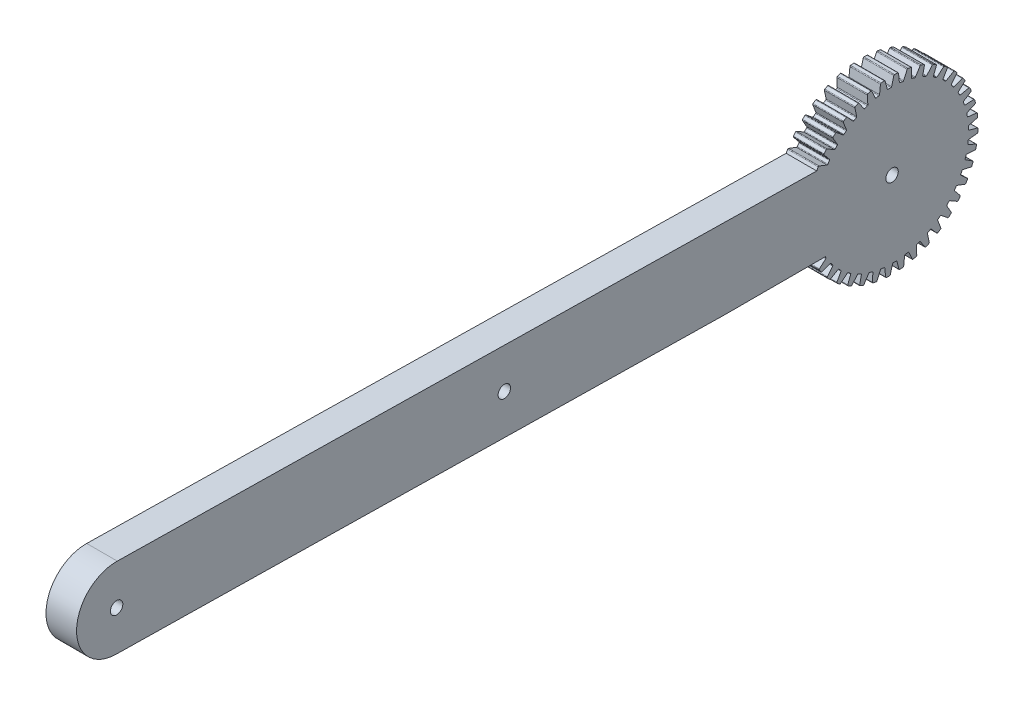
SolidWorks part; units mm, degrees
ref_plane "Front Plane" through (0, 0, 0) normal (0, 0, 1) x (1, 0, 0)
ref_plane "Top Plane" through (0, 0, 0) normal (0, 1, 0) x (1, 0, 0)
ref_plane "Right Plane" through (0, 0, 0) normal (1, 0, 0) x (0, 0, -1)
sketch "Sketch2" plane through (0, 0, 0) normal (1, 0, 0) x (0, 0, -1)
  line L0 (0, 0) -> (-202.971, 3.4315) construction
  line L1 (-0.1772, -10.4815) -> (-203.1482, -7.0501)
  line L2 (0.1772, 10.4815) -> (-202.7938, 13.913)
  arc A0 (-0.1772, -10.4815) -> (0.1772, 10.4815) centre (0, 0) ccw
  arc A1 (-202.7938, 13.913) -> (-203.1482, -7.0501) centre (-202.971, 3.4315) ccw
  circle A2 centre (-202.971, 3.4315) radius 1.625
  circle A3 centre (-101.4855, 1.7157) radius 1.625
  circle A4 centre (0, 0) radius 1.625
  circle A5 centre (0, 0) radius 44.6702
  point P3 (-101.4855, 1.7157)
  point P15 (0, 0)
  dimension "D1" = 3.25
  dimension "D2" = 3.25
  dimension "D3" = 3.25
extrude "Boss-Extrude1" add sketch "Sketch2" along normal blind 8 contours L1 A5 L2 A0 | A4 A5 L1 A0 L2 | A5 L2 A1 L1 A3 A2 region at (0, -0.1984, -11.7372) region at (0, 0.3059, 18.0947) region at (0, 2.1577, 127.6262)
extrude "Cut-Extrude1" cut sketch "Sketch3" against normal through all contours S319 A159 S318 L477 E317 L476 E316 L475 S317 A158 S316 L474 E315 L473 E314 L472 S315 A157 S314 L471 E313 L470 E312 L469 S313 A156 S312 L468 E311 L467 E310 L466 S311 A155 S310 L465 E309 L464 E308 L463 S309 A154 S308 L462 E307 L461 E306 L460 S307 A153 S306 region at (42.0599, 13.0326, 41.9132)
sketch "Sketch3" plane through (42.0599, -65.896, -38.7893) normal (1, 0, 0) x (0, 0, -1)
  line L6 (-58.518, 76.714) -> (-241.5831, 79.809)
  line L7 (-58.518, 76.714) -> (-38.1276, 76.3693)
  line L9 (-82.3831, 56.1484) -> (-241.9375, 58.8459)
  line L10 (-82.3831, 56.1484) -> (12.7743, 56.1484)
  line L128 (-59.4719, 53.9107) -> (-57.6105, 53.9107)
  line L130 (-58.7593, 76.696) -> (-58.5279, 76.696)
  line L360 (-40.0451, 86.0445) -> (-40.611, 88.1563)
  line L361 (-41.8285, 88.035) -> (-42.0659, 85.7767)
  line L362 (-42.2346, 85.5996) -> (-42.9663, 85.4837)
  line L363 (-43.1816, 85.6) -> (-44.0708, 87.5973)
  line L364 (-45.2544, 87.287) -> (-45.1356, 85.0194)
  line L365 (-45.2746, 84.818) -> (-45.9791, 84.5891)
  line L366 (-46.2099, 84.6703) -> (-47.4007, 86.5039)
  line L367 (-48.5211, 86.0123) -> (-48.049, 83.7911)
  line L368 (-48.1548, 83.5706) -> (-48.8149, 83.2342)
  line L369 (-49.0555, 83.2783) -> (-50.5184, 84.9031)
  line L370 (-51.5482, 84.2422) -> (-50.7344, 82.1223)
  line L371 (-50.8044, 81.8879) -> (-51.4037, 81.4524)
  line L372 (-51.6483, 81.4583) -> (-53.3474, 82.8343)
  line L373 (-54.2611, 82.0204) -> (-53.1257, 80.0539)
  line L374 (-53.1581, 79.8114) -> (-53.682, 79.2876)
  line L375 (-53.9245, 79.2552) -> (-55.8179, 80.3483)
  line L376 (-56.593, 79.4016) -> (-55.164, 77.6369)
  line L377 (-55.1581, 77.3923) -> (-55.5935, 76.793)
  line L378 (-55.828, 76.723) -> (-57.8691, 77.5066)
  line L379 (-58.4866, 76.4502) -> (-56.7991, 74.9308)
  line L380 (-56.755, 74.6902) -> (-57.0913, 74.0301)
  line L381 (-57.3119, 73.9243) -> (-59.4505, 74.3789)
  line L382 (-59.8951, 73.239) -> (-57.9907, 72.0022)
  line L383 (-57.9095, 71.7714) -> (-58.1385, 71.0669)
  line L384 (-58.3398, 70.9279) -> (-60.5231, 71.0423)
  line L385 (-60.784, 69.8469) -> (-58.7095, 68.9233)
  line L386 (-58.5933, 68.708) -> (-58.7091, 67.9763)
  line L387 (-58.8862, 67.8076) -> (-61.0606, 67.5791)
  line L388 (-61.1312, 66.3575) -> (-58.9379, 65.7698)
  line L389 (-58.7893, 65.5754) -> (-58.7893, 64.8346)
  line L390 (-58.9379, 64.6402) -> (-61.0497, 64.0743)
  line L391 (-60.9284, 62.8568) -> (-58.6701, 62.6194)
  line L392 (-58.493, 62.4507) -> (-58.3771, 61.719)
  line L393 (-58.4934, 61.5037) -> (-60.4907, 60.6145)
  line L394 (-60.1804, 59.4309) -> (-57.9127, 59.5497)
  line L395 (-57.7114, 59.4108) -> (-57.4825, 58.7062)
  line L396 (-57.5637, 58.4754) -> (-59.3973, 57.2847)
  line L397 (-58.9057, 56.1642) -> (-56.6845, 56.6363)
  line L398 (-56.4639, 56.5305) -> (-56.1276, 55.8705)
  line L399 (-56.1717, 55.6298) -> (-57.7965, 54.1669)
  line L400 (-57.1356, 53.1371) -> (-55.0157, 53.9509)
  line L401 (-54.7813, 53.8809) -> (-54.3458, 53.2816)
  line L402 (-54.3517, 53.037) -> (-55.7276, 51.3379)
  line L403 (-54.9138, 50.4242) -> (-52.9473, 51.5596)
  line L404 (-52.7048, 51.5272) -> (-52.181, 51.0033)
  line L405 (-52.1485, 50.7609) -> (-53.2417, 48.8674)
  line L406 (-52.295, 48.0923) -> (-50.5303, 49.5213)
  line L407 (-50.2857, 49.5272) -> (-49.6864, 49.0918)
  line L408 (-49.6164, 48.8574) -> (-50.3999, 46.8162)
  line L409 (-49.3436, 46.1987) -> (-47.8242, 47.8862)
  line L410 (-47.5835, 47.9303) -> (-46.9235, 47.594)
  line L411 (-46.8177, 47.3734) -> (-47.2723, 45.2348)
  line L412 (-46.1323, 44.7902) -> (-44.8956, 46.6946)
  line L413 (-44.6648, 46.7758) -> (-43.9602, 46.5469)
  line L414 (-43.8213, 46.3455) -> (-43.9357, 44.1622)
  line L415 (-42.7402, 43.9013) -> (-41.8166, 45.9758)
  line L416 (-41.6014, 46.0921) -> (-40.8697, 45.9762)
  line L417 (-40.701, 45.7991) -> (-40.4724, 43.6247)
  line L418 (-39.2509, 43.5541) -> (-38.6632, 45.7475)
  line L419 (-38.4688, 45.896) -> (-37.728, 45.896)
  line L420 (-37.5336, 45.7475) -> (-36.9677, 43.6356)
  line L421 (-35.7502, 43.7569) -> (-35.5128, 46.0153)
  line L422 (-35.344, 46.1924) -> (-34.6123, 46.3082)
  line L423 (-34.3971, 46.192) -> (-33.5078, 44.1946)
  line L424 (-32.3243, 44.5049) -> (-32.4431, 46.7726)
  line L425 (-32.3041, 46.9739) -> (-31.5996, 47.2028)
  line L426 (-31.3688, 47.1216) -> (-30.178, 45.288)
  line L427 (-29.0576, 45.7797) -> (-29.5297, 48.0008)
  line L428 (-29.4239, 48.2214) -> (-28.7638, 48.5577)
  line L429 (-28.5232, 48.5136) -> (-27.0603, 46.8888)
  line L430 (-26.0305, 47.5497) -> (-26.8443, 49.6696)
  line L431 (-26.7743, 49.9041) -> (-26.175, 50.3395)
  line L432 (-25.9304, 50.3336) -> (-24.2313, 48.9577)
  line L433 (-23.3176, 49.7715) -> (-24.453, 51.738)
  line L434 (-24.4205, 51.9805) -> (-23.8967, 52.5043)
  line L435 (-23.6542, 52.5368) -> (-21.7608, 51.4436)
  line L436 (-20.9857, 52.3903) -> (-22.4147, 54.1551)
  line L437 (-22.4206, 54.3996) -> (-21.9851, 54.9989)
  line L438 (-21.7507, 55.0689) -> (-19.7096, 54.2854)
  line L439 (-19.0921, 55.3417) -> (-20.7796, 56.8612)
  line L440 (-20.8237, 57.1018) -> (-20.4874, 57.7619)
  line L441 (-20.2668, 57.8676) -> (-18.1282, 57.4131)
  line L442 (-17.6836, 58.553) -> (-19.588, 59.7897)
  line L443 (-19.6692, 60.0205) -> (-19.4402, 60.7251)
  line L444 (-19.2389, 60.864) -> (-17.0556, 60.7496)
  line L445 (-16.7947, 61.9451) -> (-18.8692, 62.8687)
  line L446 (-18.9854, 63.0839) -> (-18.8695, 63.8156)
  line L447 (-18.6924, 63.9844) -> (-16.5181, 64.2129)
  line L448 (-16.4474, 65.4344) -> (-18.6408, 66.0221)
  line L449 (-18.7893, 66.2165) -> (-18.7893, 66.9574)
  line L450 (-18.6408, 67.1517) -> (-16.529, 67.7176)
  line L451 (-16.6503, 68.9352) -> (-18.9086, 69.1725)
  line L452 (-19.0857, 69.3413) -> (-19.2016, 70.073)
  line L453 (-19.0853, 70.2882) -> (-17.088, 71.1775)
  line L454 (-17.3983, 72.3611) -> (-19.666, 72.2422)
  line L455 (-19.8673, 72.3812) -> (-20.0962, 73.0857)
  line L456 (-20.015, 73.3165) -> (-18.1814, 74.5073)
  line L457 (-18.673, 75.6277) -> (-20.8942, 75.1556)
  line L458 (-21.1147, 75.2614) -> (-21.4511, 75.9215)
  line L459 (-21.407, 76.1621) -> (-19.7822, 77.6251)
  line L460 (-20.4431, 78.6548) -> (-22.563, 77.8411)
  line L461 (-22.7974, 77.911) -> (-23.2329, 78.5104)
  line L462 (-23.227, 78.7549) -> (-21.8511, 80.454)
  line L463 (-22.6649, 81.3677) -> (-24.6314, 80.2323)
  line L464 (-24.8739, 80.2648) -> (-25.3977, 80.7886)
  line L465 (-25.4302, 81.0311) -> (-24.337, 82.9245)
  line L466 (-25.2837, 83.6997) -> (-27.0484, 82.2706)
  line L467 (-27.293, 82.2647) -> (-27.8923, 82.7002)
  line L468 (-27.9623, 82.9346) -> (-27.1788, 84.9757)
  line L469 (-28.2351, 85.5932) -> (-29.7545, 83.9057)
  line L470 (-29.9952, 83.8616) -> (-30.6552, 84.198)
  line L471 (-30.761, 84.4185) -> (-30.3064, 86.5571)
  line L472 (-31.4464, 87.0018) -> (-32.6831, 85.0973)
  line L473 (-32.9139, 85.0162) -> (-33.6184, 85.2451)
  line L474 (-33.7574, 85.4464) -> (-33.643, 87.6298)
  line L475 (-34.8384, 87.8906) -> (-35.762, 85.8162)
  line L476 (-35.9773, 85.6999) -> (-36.709, 85.8158)
  line L477 (-36.8777, 85.9929) -> (-37.1063, 88.1672)
  line L478 (-38.3278, 88.2379) -> (-38.9155, 86.0445)
  line L479 (-39.1099, 85.896) -> (-39.8507, 85.896)
  circle A40 centre (-38.7893, 65.896) radius 65.1946
  arc A120 (-40.8234, 88.3038) -> (-41.654, 88.2129) centre (-38.7893, 65.896) ccw
  arc A121 (-44.3037, 87.7098) -> (-45.1098, 87.49) centre (-38.7893, 65.896) ccw
  arc A122 (-47.6482, 86.5786) -> (-48.4101, 86.2354) centre (-38.7893, 65.896) ccw
  arc A123 (-50.7747, 84.9381) -> (-51.4734, 84.48) centre (-38.7893, 65.896) ccw
  arc A124 (-53.6059, 82.8287) -> (-54.2244, 82.2669) centre (-38.7893, 65.896) ccw
  arc A125 (-56.0724, 80.3024) -> (-56.5954, 79.6508) centre (-38.7893, 65.896) ccw
  arc A126 (-58.1133, 77.4214) -> (-58.5279, 76.696) centre (-38.7893, 65.896) ccw
  arc A127 (-59.6783, 74.2566) -> (-59.9744, 73.4752) centre (-38.7893, 65.896) ccw
  arc A128 (-60.729, 70.8859) -> (-60.8992, 70.0679) centre (-38.7893, 65.896) ccw
  arc A129 (-61.2395, 67.3923) -> (-61.2796, 66.5578) centre (-38.7893, 65.896) ccw
  arc A130 (-61.1972, 63.8619) -> (-61.1062, 63.0314) centre (-38.7893, 65.896) ccw
  arc A131 (-60.6031, 60.3816) -> (-60.3834, 59.5755) centre (-38.7893, 65.896) ccw
  arc A132 (-59.4719, 57.0371) -> (-59.1288, 56.2753) centre (-38.7893, 65.896) ccw
  arc A133 (-57.8315, 53.9107) -> (-57.3733, 53.2119) centre (-38.7893, 65.896) ccw
  arc A134 (-55.7221, 51.0794) -> (-55.1603, 50.4609) centre (-38.7893, 65.896) ccw
  arc A135 (-53.1958, 48.6129) -> (-52.5442, 48.09) centre (-38.7893, 65.896) ccw
  arc A136 (-50.3148, 46.572) -> (-49.5894, 46.1574) centre (-38.7893, 65.896) ccw
  arc A137 (-47.15, 45.007) -> (-46.3686, 44.711) centre (-38.7893, 65.896) ccw
  arc A138 (-43.7793, 43.9563) -> (-42.9612, 43.7861) centre (-38.7893, 65.896) ccw
  arc A139 (-40.2857, 43.4458) -> (-39.4511, 43.4057) centre (-38.7893, 65.896) ccw
  arc A140 (-36.7553, 43.4881) -> (-35.9247, 43.5791) centre (-38.7893, 65.896) ccw
  arc A141 (-33.275, 44.0822) -> (-32.4689, 44.302) centre (-38.7893, 65.896) ccw
  arc A142 (-29.9304, 45.2134) -> (-29.1686, 45.5566) centre (-38.7893, 65.896) ccw
  arc A143 (-26.804, 46.8539) -> (-26.1053, 47.312) centre (-38.7893, 65.896) ccw
  arc A144 (-23.9727, 48.9632) -> (-23.3543, 49.525) centre (-38.7893, 65.896) ccw
  arc A145 (-21.5063, 51.4895) -> (-20.9833, 52.1411) centre (-38.7893, 65.896) ccw
  arc A146 (-19.4654, 54.3705) -> (-19.0508, 55.0959) centre (-38.7893, 65.896) ccw
  arc A147 (-17.9003, 57.5354) -> (-17.6043, 58.3167) centre (-38.7893, 65.896) ccw
  arc A148 (-16.8496, 60.9061) -> (-16.6795, 61.7241) centre (-38.7893, 65.896) ccw
  arc A149 (-16.3392, 64.3996) -> (-16.2991, 65.2342) centre (-38.7893, 65.896) ccw
  arc A150 (-16.3815, 67.93) -> (-16.4724, 68.7606) centre (-38.7893, 65.896) ccw
  arc A151 (-16.9755, 71.4103) -> (-17.1953, 72.2164) centre (-38.7893, 65.896) ccw
  arc A152 (-18.1067, 74.7549) -> (-18.4499, 75.5167) centre (-38.7893, 65.896) ccw
  arc A153 (-19.7472, 77.8813) -> (-20.2053, 78.58) centre (-38.7893, 65.896) ccw
  arc A154 (-21.8566, 80.7126) -> (-22.4184, 81.331) centre (-38.7893, 65.896) ccw
  arc A155 (-24.3829, 83.179) -> (-25.0345, 83.702) centre (-38.7893, 65.896) ccw
  arc A156 (-27.2639, 85.2199) -> (-27.9893, 85.6345) centre (-38.7893, 65.896) ccw
  arc A157 (-30.4287, 86.785) -> (-31.2101, 87.081) centre (-38.7893, 65.896) ccw
  arc A158 (-33.7994, 87.8357) -> (-34.6175, 88.0058) centre (-38.7893, 65.896) ccw
  arc A159 (-37.293, 88.3462) -> (-38.1276, 88.3862) centre (-38.7893, 65.896) ccw
  ellipse E240 centre (-42.2659, 85.7971) end of major axis (-42.4646, 85.7657) minor radius 0.2 (-42.2346, 85.5996) -> (-42.0659, 85.7767) ccw
  ellipse E241 centre (-42.9976, 85.6812) end of major axis (-43.1963, 85.6498) minor radius 0.2 (-43.1816, 85.6) -> (-42.9663, 85.4837) ccw
  ellipse E242 centre (-45.3364, 85.0083) end of major axis (-45.5277, 84.9461) minor radius 0.2 (-45.2746, 84.818) -> (-45.1356, 85.0194) ccw
  ellipse E243 centre (-46.0409, 84.7793) end of major axis (-46.2322, 84.7172) minor radius 0.2 (-46.2099, 84.6703) -> (-45.9791, 84.5891) ccw
  ellipse E244 centre (-48.2456, 83.7488) end of major axis (-48.4248, 83.6574) minor radius 0.2 (-48.1548, 83.5706) -> (-48.049, 83.7911) ccw
  ellipse E245 centre (-48.9056, 83.4124) end of major axis (-49.0849, 83.3211) minor radius 0.2 (-49.0555, 83.2783) -> (-48.8149, 83.2342) ccw
  ellipse E246 centre (-50.9219, 82.0497) end of major axis (-51.0847, 81.9315) minor radius 0.2 (-50.8044, 81.8879) -> (-50.7344, 82.1223) ccw
  ellipse E247 centre (-51.5213, 81.6143) end of major axis (-51.684, 81.496) minor radius 0.2 (-51.6483, 81.4583) -> (-51.4037, 81.4524) ccw
  ellipse E248 centre (-53.2996, 79.9529) end of major axis (-53.4418, 79.8106) minor radius 0.2 (-53.1581, 79.8114) -> (-53.1257, 80.0539) ccw
  ellipse E249 centre (-53.8234, 79.429) end of major axis (-53.9657, 79.2868) minor radius 0.2 (-53.9245, 79.2552) -> (-53.682, 79.2876) ccw
  ellipse E250 centre (-55.3199, 77.5099) end of major axis (-55.4381, 77.3472) minor radius 0.2 (-55.1581, 77.3923) -> (-55.164, 77.6369) ccw
  ellipse E251 centre (-55.7554, 76.9106) end of major axis (-55.8736, 76.7478) minor radius 0.2 (-55.828, 76.723) -> (-55.5935, 76.793) ccw
  ellipse E252 centre (-56.9332, 74.781) end of major axis (-57.0245, 74.6017) minor radius 0.2 (-56.755, 74.6902) -> (-56.7991, 74.9308) ccw
  ellipse E253 centre (-57.2695, 74.1209) end of major axis (-57.3609, 73.9416) minor radius 0.2 (-57.3119, 73.9243) -> (-57.0913, 74.0301) ccw
  ellipse E254 centre (-58.0997, 71.8332) end of major axis (-58.1619, 71.6419) minor radius 0.2 (-57.9095, 71.7714) -> (-57.9907, 72.0022) ccw
  ellipse E255 centre (-58.3287, 71.1287) end of major axis (-58.3908, 70.9374) minor radius 0.2 (-58.3398, 70.9279) -> (-58.1385, 71.0669) ccw
  ellipse E256 centre (-58.7908, 68.7393) end of major axis (-58.8223, 68.5407) minor radius 0.2 (-58.5933, 68.708) -> (-58.7095, 68.9233) ccw
  ellipse E257 centre (-58.9067, 68.0076) end of major axis (-58.9382, 67.8089) minor radius 0.2 (-58.8862, 67.8076) -> (-58.7091, 67.9763) ccw
  ellipse E258 centre (-58.9893, 65.5754) end of major axis (-58.9893, 65.3743) minor radius 0.2 (-58.7893, 65.5754) -> (-58.9379, 65.7698) ccw
  ellipse E259 centre (-58.9893, 64.8346) end of major axis (-58.9893, 64.6334) minor radius 0.2 (-58.9379, 64.6402) -> (-58.7893, 64.8346) ccw
  ellipse E260 centre (-58.6905, 62.4194) end of major axis (-58.659, 62.2207) minor radius 0.2 (-58.493, 62.4507) -> (-58.6701, 62.6194) ccw
  ellipse E261 centre (-58.5746, 61.6877) end of major axis (-58.5431, 61.489) minor radius 0.2 (-58.4934, 61.5037) -> (-58.3771, 61.719) ccw
  ellipse E262 centre (-57.9016, 59.349) end of major axis (-57.8395, 59.1576) minor radius 0.2 (-57.7114, 59.4108) -> (-57.9127, 59.5497) ccw
  ellipse E263 centre (-57.6727, 58.6444) end of major axis (-57.6105, 58.4531) minor radius 0.2 (-57.5637, 58.4754) -> (-57.4825, 58.7062) ccw
  ellipse E264 centre (-56.6421, 56.4397) end of major axis (-56.5508, 56.2605) minor radius 0.2 (-56.4639, 56.5305) -> (-56.6845, 56.6363) ccw
  ellipse E265 centre (-56.3058, 55.7797) end of major axis (-56.2145, 55.6004) minor radius 0.2 (-56.1717, 55.6298) -> (-56.1276, 55.8705) ccw
  ellipse E266 centre (-54.9431, 53.7634) end of major axis (-54.8248, 53.6006) minor radius 0.2 (-54.7813, 53.8809) -> (-55.0157, 53.9509) ccw
  ellipse E267 centre (-54.5076, 53.164) end of major axis (-54.3894, 53.0013) minor radius 0.2 (-54.3517, 53.037) -> (-54.3458, 53.2816) ccw
  ellipse E268 centre (-52.8462, 51.3857) end of major axis (-52.704, 51.2435) minor radius 0.2 (-52.7048, 51.5272) -> (-52.9473, 51.5596) ccw
  ellipse E269 centre (-52.3224, 50.8619) end of major axis (-52.1801, 50.7197) minor radius 0.2 (-52.1485, 50.7609) -> (-52.181, 51.0033) ccw
  ellipse E270 centre (-50.4033, 49.3654) end of major axis (-50.2405, 49.2472) minor radius 0.2 (-50.2857, 49.5272) -> (-50.5303, 49.5213) ccw
  ellipse E271 centre (-49.8039, 48.93) end of major axis (-49.6412, 48.8117) minor radius 0.2 (-49.6164, 48.8574) -> (-49.6864, 49.0918) ccw
  ellipse E272 centre (-47.6743, 47.7521) end of major axis (-47.4951, 47.6608) minor radius 0.2 (-47.5835, 47.9303) -> (-47.8242, 47.8862) ccw
  ellipse E273 centre (-47.0143, 47.4158) end of major axis (-46.835, 47.3245) minor radius 0.2 (-46.8177, 47.3734) -> (-46.9235, 47.594) ccw
  ellipse E274 centre (-44.7266, 46.5856) end of major axis (-44.5353, 46.5234) minor radius 0.2 (-44.6648, 46.7758) -> (-44.8956, 46.6946) ccw
  ellipse E275 centre (-44.0221, 46.3566) end of major axis (-43.8307, 46.2945) minor radius 0.2 (-43.8213, 46.3455) -> (-43.9602, 46.5469) ccw
  ellipse E276 centre (-41.6327, 45.8945) end of major axis (-41.434, 45.8631) minor radius 0.2 (-41.6014, 46.0921) -> (-41.8166, 45.9758) ccw
  ellipse E277 centre (-40.901, 45.7786) end of major axis (-40.7023, 45.7472) minor radius 0.2 (-40.701, 45.7991) -> (-40.8697, 45.9762) ccw
  ellipse E278 centre (-38.4688, 45.696) end of major axis (-38.2676, 45.696) minor radius 0.2 (-38.4688, 45.896) -> (-38.6632, 45.7475) ccw
  ellipse E279 centre (-37.728, 45.696) end of major axis (-37.5268, 45.696) minor radius 0.2 (-37.5336, 45.7475) -> (-37.728, 45.896) ccw
  ellipse E280 centre (-35.3128, 45.9948) end of major axis (-35.1141, 46.0263) minor radius 0.2 (-35.344, 46.1924) -> (-35.5128, 46.0153) ccw
  ellipse E281 centre (-34.5811, 46.1107) end of major axis (-34.3824, 46.1422) minor radius 0.2 (-34.3971, 46.192) -> (-34.6123, 46.3082) ccw
  ellipse E282 centre (-32.2423, 46.7837) end of major axis (-32.051, 46.8459) minor radius 0.2 (-32.3041, 46.9739) -> (-32.4431, 46.7726) ccw
  ellipse E283 centre (-31.5378, 47.0126) end of major axis (-31.3464, 47.0748) minor radius 0.2 (-31.3688, 47.1216) -> (-31.5996, 47.2028) ccw
  ellipse E284 centre (-29.3331, 48.0432) end of major axis (-29.1539, 48.1345) minor radius 0.2 (-29.4239, 48.2214) -> (-29.5297, 48.0008) ccw
  ellipse E285 centre (-28.673, 48.3795) end of major axis (-28.4938, 48.4708) minor radius 0.2 (-28.5232, 48.5136) -> (-28.7638, 48.5577) ccw
  ellipse E286 centre (-26.6567, 49.7422) end of major axis (-26.494, 49.8605) minor radius 0.2 (-26.7743, 49.9041) -> (-26.8443, 49.6696) ccw
  ellipse E287 centre (-26.0574, 50.1777) end of major axis (-25.8947, 50.2959) minor radius 0.2 (-25.9304, 50.3336) -> (-26.175, 50.3395) ccw
  ellipse E288 centre (-24.2791, 51.8391) end of major axis (-24.1369, 51.9813) minor radius 0.2 (-24.4205, 51.9805) -> (-24.453, 51.738) ccw
  ellipse E289 centre (-23.7553, 52.3629) end of major axis (-23.613, 52.5052) minor radius 0.2 (-23.6542, 52.5368) -> (-23.8967, 52.5043) ccw
  ellipse E290 centre (-22.2588, 54.282) end of major axis (-22.1405, 54.4448) minor radius 0.2 (-22.4206, 54.3996) -> (-22.4147, 54.1551) ccw
  ellipse E291 centre (-21.8233, 54.8814) end of major axis (-21.7051, 55.0441) minor radius 0.2 (-21.7507, 55.0689) -> (-21.9851, 54.9989) ccw
  ellipse E292 centre (-20.6455, 57.011) end of major axis (-20.5542, 57.1902) minor radius 0.2 (-20.8237, 57.1018) -> (-20.7796, 56.8612) ccw
  ellipse E293 centre (-20.3092, 57.6711) end of major axis (-20.2178, 57.8503) minor radius 0.2 (-20.2668, 57.8676) -> (-20.4874, 57.7619) ccw
  ellipse E294 centre (-19.4789, 59.9587) end of major axis (-19.4168, 60.15) minor radius 0.2 (-19.6692, 60.0205) -> (-19.588, 59.7897) ccw
  ellipse E295 centre (-19.25, 60.6633) end of major axis (-19.1879, 60.8546) minor radius 0.2 (-19.2389, 60.864) -> (-19.4402, 60.7251) ccw
  ellipse E296 centre (-18.7879, 63.0526) end of major axis (-18.7564, 63.2513) minor radius 0.2 (-18.9854, 63.0839) -> (-18.8692, 62.8687) ccw
  ellipse E297 centre (-18.672, 63.7843) end of major axis (-18.6405, 63.983) minor radius 0.2 (-18.6924, 63.9844) -> (-18.8695, 63.8156) ccw
  ellipse E298 centre (-18.5893, 66.2165) end of major axis (-18.5893, 66.4177) minor radius 0.2 (-18.7893, 66.2165) -> (-18.6408, 66.0221) ccw
  ellipse E299 centre (-18.5893, 66.9574) end of major axis (-18.5893, 67.1585) minor radius 0.2 (-18.6408, 67.1517) -> (-18.7893, 66.9574) ccw
  ellipse E300 centre (-18.8882, 69.3726) end of major axis (-18.9197, 69.5712) minor radius 0.2 (-19.0857, 69.3413) -> (-18.9086, 69.1725) ccw
  ellipse E301 centre (-19.0041, 70.1043) end of major axis (-19.0355, 70.303) minor radius 0.2 (-19.0853, 70.2882) -> (-19.2016, 70.073) ccw
  ellipse E302 centre (-19.6771, 72.443) end of major axis (-19.7392, 72.6343) minor radius 0.2 (-19.8673, 72.3812) -> (-19.666, 72.2422) ccw
  ellipse E303 centre (-19.906, 73.1476) end of major axis (-19.9681, 73.3389) minor radius 0.2 (-20.015, 73.3165) -> (-20.0962, 73.0857) ccw
  ellipse E304 centre (-20.9365, 75.3522) end of major axis (-21.0279, 75.5314) minor radius 0.2 (-21.1147, 75.2614) -> (-20.8942, 75.1556) ccw
  ellipse E305 centre (-21.2729, 76.0123) end of major axis (-21.3642, 76.1915) minor radius 0.2 (-21.407, 76.1621) -> (-21.4511, 75.9215) ccw
  ellipse E306 centre (-22.6356, 78.0286) end of major axis (-22.7539, 78.1913) minor radius 0.2 (-22.7974, 77.911) -> (-22.563, 77.8411) ccw
  ellipse E307 centre (-23.0711, 78.6279) end of major axis (-23.1893, 78.7907) minor radius 0.2 (-23.227, 78.7549) -> (-23.2329, 78.5104) ccw
  ellipse E308 centre (-24.7325, 80.4062) end of major axis (-24.8747, 80.5484) minor radius 0.2 (-24.8739, 80.2648) -> (-24.6314, 80.2323) ccw
  ellipse E309 centre (-25.2563, 80.93) end of major axis (-25.3985, 81.0723) minor radius 0.2 (-25.4302, 81.0311) -> (-25.3977, 80.7886) ccw
  ellipse E310 centre (-27.1754, 82.4265) end of major axis (-27.3382, 82.5448) minor radius 0.2 (-27.293, 82.2647) -> (-27.0484, 82.2706) ccw
  ellipse E311 centre (-27.7748, 82.862) end of major axis (-27.9375, 82.9802) minor radius 0.2 (-27.9623, 82.9346) -> (-27.8923, 82.7002) ccw
  ellipse E312 centre (-29.9044, 84.0398) end of major axis (-30.0836, 84.1312) minor radius 0.2 (-29.9952, 83.8616) -> (-29.7545, 83.9057) ccw
  ellipse E313 centre (-30.5644, 84.3762) end of major axis (-30.7437, 84.4675) minor radius 0.2 (-30.761, 84.4185) -> (-30.6552, 84.198) ccw
  ellipse E314 centre (-32.8521, 85.2064) end of major axis (-33.0434, 85.2685) minor radius 0.2 (-32.9139, 85.0162) -> (-32.6831, 85.0973) ccw
  ellipse E315 centre (-33.5566, 85.4353) end of major axis (-33.748, 85.4975) minor radius 0.2 (-33.7574, 85.4464) -> (-33.6184, 85.2451) ccw
  ellipse E316 centre (-35.946, 85.8974) end of major axis (-36.1447, 85.9289) minor radius 0.2 (-35.9773, 85.6999) -> (-35.762, 85.8162) ccw
  ellipse E317 centre (-36.6777, 86.0133) end of major axis (-36.8764, 86.0448) minor radius 0.2 (-36.8777, 85.9929) -> (-36.709, 85.8158) ccw
  ellipse E318 centre (-39.1099, 86.096) end of major axis (-39.3111, 86.096) minor radius 0.2 (-39.1099, 85.896) -> (-38.9155, 86.0445) ccw
  ellipse E319 centre (-39.8507, 86.096) end of major axis (-40.0519, 86.096) minor radius 0.2 (-40.0451, 86.0445) -> (-39.8507, 85.896) ccw
  spline S240 degree 3 poles (-40.611, 88.1563) (-40.6232, 88.2019) (-40.652, 88.2423) (-40.7285, 88.2953) (-40.7764, 88.3081) (-40.8234, 88.3038) knots 0 0 0 0 0.5 0.5 1 1 1 1
  spline S241 degree 3 poles (-41.654, 88.2129) (-41.6988, 88.2071) (-41.7405, 88.1865) (-41.8038, 88.1221) (-41.8238, 88.08) (-41.8285, 88.035) knots 0 0 0 0 0.5 0.5 1 1 1 1
  spline S242 degree 3 poles (-44.0708, 87.5973) (-44.09, 87.6404) (-44.1248, 87.6758) (-44.2087, 87.7162) (-44.258, 87.7213) (-44.3037, 87.7098) knots 0 0 0 0 0.5 0.5 1 1 1 1
  spline S243 degree 3 poles (-45.1098, 87.49) (-45.1532, 87.4773) (-45.1911, 87.4504) (-45.2436, 87.3769) (-45.2568, 87.3322) (-45.2544, 87.287) knots 0 0 0 0 0.5 0.5 1 1 1 1
  spline S244 degree 3 poles (-47.4007, 86.5039) (-47.4264, 86.5435) (-47.4663, 86.573) (-47.5554, 86.5998) (-47.6049, 86.5971) (-47.6482, 86.5786) knots 0 0 0 0 0.5 0.5 1 1 1 1
  spline S245 degree 3 poles (-48.4101, 86.2354) (-48.4509, 86.2161) (-48.4842, 86.1836) (-48.5245, 86.1028) (-48.5305, 86.0565) (-48.5211, 86.0123) knots 0 0 0 0 0.5 0.5 1 1 1 1
  spline S246 degree 3 poles (-50.5184, 84.9031) (-50.55, 84.9382) (-50.594, 84.9611) (-50.6863, 84.9736) (-50.7347, 84.9632) (-50.7747, 84.9381) knots 0 0 0 0 0.5 0.5 1 1 1 1
  spline S247 degree 3 poles (-51.4734, 84.48) (-51.5107, 84.4545) (-51.5385, 84.4172) (-51.5657, 84.3311) (-51.5644, 84.2845) (-51.5482, 84.2422) knots 0 0 0 0 0.5 0.5 1 1 1 1
  spline S248 degree 3 poles (-53.3474, 82.8343) (-53.3841, 82.864) (-53.4311, 82.8797) (-53.5242, 82.8776) (-53.5704, 82.8598) (-53.6059, 82.8287) knots 0 0 0 0 0.5 0.5 1 1 1 1
  spline S249 degree 3 poles (-54.2244, 82.2669) (-54.2573, 82.2359) (-54.2789, 82.1947) (-54.2923, 82.1054) (-54.2837, 82.0596) (-54.2611, 82.0204) knots 0 0 0 0 0.5 0.5 1 1 1 1
  spline S250 degree 3 poles (-55.8179, 80.3483) (-55.8588, 80.3719) (-55.9077, 80.3801) (-55.9993, 80.3635) (-56.0422, 80.3387) (-56.0724, 80.3024) knots 0 0 0 0 0.5 0.5 1 1 1 1
  spline S251 degree 3 poles (-56.5954, 79.6508) (-56.623, 79.615) (-56.6379, 79.571) (-56.6371, 79.4807) (-56.6215, 79.4368) (-56.593, 79.4016) knots 0 0 0 0 0.5 0.5 1 1 1 1
  spline S252 degree 3 poles (-57.8691, 77.5066) (-57.9132, 77.5235) (-57.9628, 77.5239) (-58.0506, 77.4932) (-58.0891, 77.4619) (-58.1133, 77.4214) knots 0 0 0 0 0.5 0.5 1 1 1 1
  spline S253 degree 3 poles (-58.5279, 76.696) (-58.5496, 76.6563) (-58.5574, 76.6105) (-58.5425, 76.5214) (-58.5202, 76.4805) (-58.4866, 76.4502) knots 0 0 0 0 0.5 0.5 1 1 1 1
  spline S254 degree 3 poles (-59.4505, 74.3789) (-59.4966, 74.3887) (-59.5457, 74.3814) (-59.6277, 74.3372) (-59.6608, 74.3004) (-59.6783, 74.2566) knots 0 0 0 0 0.5 0.5 1 1 1 1
  spline S255 degree 3 poles (-59.9744, 73.4752) (-59.9896, 73.4327) (-59.9901, 73.3862) (-59.9615, 73.3005) (-59.9331, 73.2636) (-59.8951, 73.239) knots 0 0 0 0 0.5 0.5 1 1 1 1
  spline S256 degree 3 poles (-60.5231, 71.0423) (-60.5703, 71.0448) (-60.6176, 71.0299) (-60.6916, 70.9735) (-60.7186, 70.9319) (-60.729, 70.8859) knots 0 0 0 0 0.5 0.5 1 1 1 1
  spline S257 degree 3 poles (-60.8992, 70.0679) (-60.9076, 70.0234) (-60.9008, 69.9774) (-60.8592, 69.8973) (-60.8253, 69.8653) (-60.784, 69.8469) knots 0 0 0 0 0.5 0.5 1 1 1 1
  spline S258 degree 3 poles (-61.0606, 67.5791) (-61.1076, 67.5741) (-61.152, 67.552) (-61.2163, 67.4847) (-61.2364, 67.4394) (-61.2395, 67.3923) knots 0 0 0 0 0.5 0.5 1 1 1 1
  spline S259 degree 3 poles (-61.2796, 66.5578) (-61.2809, 66.5126) (-61.2671, 66.4682) (-61.2134, 66.3956) (-61.1749, 66.3692) (-61.1312, 66.3575) knots 0 0 0 0 0.5 0.5 1 1 1 1
  spline S260 degree 3 poles (-61.0497, 64.0743) (-61.0953, 64.0621) (-61.1357, 64.0333) (-61.1887, 63.9568) (-61.2015, 63.9089) (-61.1972, 63.8619) knots 0 0 0 0 0.5 0.5 1 1 1 1
  spline S261 degree 3 poles (-61.1062, 63.0314) (-61.1005, 62.9865) (-61.0798, 62.9448) (-61.0155, 62.8815) (-60.9734, 62.8615) (-60.9284, 62.8568) knots 0 0 0 0 0.5 0.5 1 1 1 1
  spline S262 degree 3 poles (-60.4907, 60.6145) (-60.5338, 60.5953) (-60.5692, 60.5605) (-60.6096, 60.4766) (-60.6147, 60.4274) (-60.6031, 60.3816) knots 0 0 0 0 0.5 0.5 1 1 1 1
  spline S263 degree 3 poles (-60.3834, 59.5755) (-60.3707, 59.5321) (-60.3438, 59.4942) (-60.2703, 59.4417) (-60.2255, 59.4285) (-60.1804, 59.4309) knots 0 0 0 0 0.5 0.5 1 1 1 1
  spline S264 degree 3 poles (-59.3973, 57.2847) (-59.4369, 57.259) (-59.4664, 57.2191) (-59.4932, 57.1299) (-59.4905, 57.0804) (-59.4719, 57.0371) knots 0 0 0 0 0.5 0.5 1 1 1 1
  spline S265 degree 3 poles (-59.1288, 56.2753) (-59.1094, 56.2344) (-59.0769, 56.2011) (-58.9961, 56.1608) (-58.9499, 56.1548) (-58.9057, 56.1642) knots 0 0 0 0 0.5 0.5 1 1 1 1
  spline S266 degree 3 poles (-57.7965, 54.1669) (-57.8315, 54.1353) (-57.8545, 54.0913) (-57.8669, 53.9991) (-57.8566, 53.9506) (-57.8315, 53.9107) knots 0 0 0 0 0.5 0.5 1 1 1 1
  spline S267 degree 3 poles (-57.3733, 53.2119) (-57.3478, 53.1746) (-57.3105, 53.1468) (-57.2244, 53.1196) (-57.1778, 53.1209) (-57.1356, 53.1371) knots 0 0 0 0 0.5 0.5 1 1 1 1
  spline S268 degree 3 poles (-55.7276, 51.3379) (-55.7573, 51.3012) (-55.7731, 51.2542) (-55.771, 51.1611) (-55.7532, 51.1149) (-55.7221, 51.0794) knots 0 0 0 0 0.5 0.5 1 1 1 1
  spline S269 degree 3 poles (-55.1603, 50.4609) (-55.1293, 50.428) (-55.0881, 50.4064) (-54.9988, 50.393) (-54.953, 50.4016) (-54.9138, 50.4242) knots 0 0 0 0 0.5 0.5 1 1 1 1
  spline S270 degree 3 poles (-53.2417, 48.8674) (-53.2653, 48.8265) (-53.2735, 48.7776) (-53.2569, 48.686) (-53.2321, 48.6431) (-53.1958, 48.6129) knots 0 0 0 0 0.5 0.5 1 1 1 1
  spline S271 degree 3 poles (-52.5442, 48.09) (-52.5084, 48.0623) (-52.4644, 48.0474) (-52.374, 48.0482) (-52.3301, 48.0638) (-52.295, 48.0923) knots 0 0 0 0 0.5 0.5 1 1 1 1
  spline S272 degree 3 poles (-50.3999, 46.8162) (-50.4168, 46.7722) (-50.4173, 46.7225) (-50.3865, 46.6347) (-50.3553, 46.5962) (-50.3148, 46.572) knots 0 0 0 0 0.5 0.5 1 1 1 1
  spline S273 degree 3 poles (-49.5894, 46.1574) (-49.5497, 46.1357) (-49.5039, 46.1279) (-49.4148, 46.1428) (-49.3739, 46.1651) (-49.3436, 46.1987) knots 0 0 0 0 0.5 0.5 1 1 1 1
  spline S274 degree 3 poles (-47.2723, 45.2348) (-47.2821, 45.1887) (-47.2747, 45.1396) (-47.2306, 45.0576) (-47.1938, 45.0245) (-47.15, 45.007) knots 0 0 0 0 0.5 0.5 1 1 1 1
  spline S275 degree 3 poles (-46.3686, 44.711) (-46.326, 44.6957) (-46.2796, 44.6952) (-46.1939, 44.7238) (-46.157, 44.7522) (-46.1323, 44.7902) knots 0 0 0 0 0.5 0.5 1 1 1 1
  spline S276 degree 3 poles (-43.9357, 44.1622) (-43.9382, 44.1151) (-43.9232, 44.0677) (-43.8669, 43.9937) (-43.8253, 43.9667) (-43.7793, 43.9563) knots 0 0 0 0 0.5 0.5 1 1 1 1
  spline S277 degree 3 poles (-42.9612, 43.7861) (-42.9168, 43.7777) (-42.8708, 43.7845) (-42.7907, 43.8261) (-42.7586, 43.86) (-42.7402, 43.9013) knots 0 0 0 0 0.5 0.5 1 1 1 1
  spline S278 degree 3 poles (-40.4724, 43.6247) (-40.4675, 43.5778) (-40.4453, 43.5333) (-40.3781, 43.469) (-40.3328, 43.4489) (-40.2857, 43.4458) knots 0 0 0 0 0.5 0.5 1 1 1 1
  spline S279 degree 3 poles (-39.4511, 43.4057) (-39.4059, 43.4044) (-39.3616, 43.4182) (-39.2889, 43.4719) (-39.2626, 43.5104) (-39.2509, 43.5541) knots 0 0 0 0 0.5 0.5 1 1 1 1
  spline S280 degree 3 poles (-36.9677, 43.6356) (-36.9555, 43.59) (-36.9267, 43.5496) (-36.8502, 43.4966) (-36.8023, 43.4838) (-36.7553, 43.4881) knots 0 0 0 0 0.5 0.5 1 1 1 1
  spline S281 degree 3 poles (-35.9247, 43.5791) (-35.8799, 43.5848) (-35.8382, 43.6055) (-35.7749, 43.6698) (-35.7549, 43.712) (-35.7502, 43.7569) knots 0 0 0 0 0.5 0.5 1 1 1 1
  spline S282 degree 3 poles (-33.5078, 44.1946) (-33.4886, 44.1515) (-33.4539, 44.1161) (-33.37, 44.0757) (-33.3207, 44.0706) (-33.275, 44.0822) knots 0 0 0 0 0.5 0.5 1 1 1 1
  spline S283 degree 3 poles (-32.4689, 44.302) (-32.4255, 44.3147) (-32.3875, 44.3416) (-32.3351, 44.415) (-32.3219, 44.4598) (-32.3243, 44.5049) knots 0 0 0 0 0.5 0.5 1 1 1 1
  spline S284 degree 3 poles (-30.178, 45.288) (-30.1523, 45.2484) (-30.1124, 45.2189) (-30.0233, 45.1922) (-29.9738, 45.1948) (-29.9304, 45.2134) knots 0 0 0 0 0.5 0.5 1 1 1 1
  spline S285 degree 3 poles (-29.1686, 45.5566) (-29.1277, 45.5759) (-29.0945, 45.6084) (-29.0542, 45.6892) (-29.0482, 45.7354) (-29.0576, 45.7797) knots 0 0 0 0 0.5 0.5 1 1 1 1
  spline S286 degree 3 poles (-27.0603, 46.8888) (-27.0287, 46.8538) (-26.9847, 46.8309) (-26.8924, 46.8184) (-26.844, 46.8287) (-26.804, 46.8539) knots 0 0 0 0 0.5 0.5 1 1 1 1
  spline S287 degree 3 poles (-26.1053, 47.312) (-26.0679, 47.3375) (-26.0402, 47.3748) (-26.013, 47.4609) (-26.0143, 47.5075) (-26.0305, 47.5497) knots 0 0 0 0 0.5 0.5 1 1 1 1
  spline S288 degree 3 poles (-24.2313, 48.9577) (-24.1946, 48.928) (-24.1475, 48.9122) (-24.0545, 48.9143) (-24.0083, 48.9321) (-23.9727, 48.9632) knots 0 0 0 0 0.5 0.5 1 1 1 1
  spline S289 degree 3 poles (-23.3543, 49.525) (-23.3214, 49.556) (-23.2998, 49.5972) (-23.2864, 49.6865) (-23.295, 49.7323) (-23.3176, 49.7715) knots 0 0 0 0 0.5 0.5 1 1 1 1
  spline S290 degree 3 poles (-21.7608, 51.4436) (-21.7199, 51.42) (-21.671, 51.4118) (-21.5794, 51.4284) (-21.5365, 51.4533) (-21.5063, 51.4895) knots 0 0 0 0 0.5 0.5 1 1 1 1
  spline S291 degree 3 poles (-20.9833, 52.1411) (-20.9557, 52.1769) (-20.9408, 52.221) (-20.9415, 52.3113) (-20.9572, 52.3552) (-20.9857, 52.3903) knots 0 0 0 0 0.5 0.5 1 1 1 1
  spline S292 degree 3 poles (-19.7096, 54.2854) (-19.6655, 54.2685) (-19.6159, 54.268) (-19.5281, 54.2988) (-19.4896, 54.33) (-19.4654, 54.3705) knots 0 0 0 0 0.5 0.5 1 1 1 1
  spline S293 degree 3 poles (-19.0508, 55.0959) (-19.0291, 55.1356) (-19.0213, 55.1815) (-19.0362, 55.2705) (-19.0585, 55.3115) (-19.0921, 55.3417) knots 0 0 0 0 0.5 0.5 1 1 1 1
  spline S294 degree 3 poles (-18.1282, 57.4131) (-18.082, 57.4033) (-18.033, 57.4106) (-17.951, 57.4547) (-17.9179, 57.4916) (-17.9003, 57.5354) knots 0 0 0 0 0.5 0.5 1 1 1 1
  spline S295 degree 3 poles (-17.6043, 58.3167) (-17.5891, 58.3593) (-17.5886, 58.4058) (-17.6172, 58.4914) (-17.6456, 58.5284) (-17.6836, 58.553) knots 0 0 0 0 0.5 0.5 1 1 1 1
  spline S296 degree 3 poles (-17.0556, 60.7496) (-17.0084, 60.7471) (-16.9611, 60.7621) (-16.8871, 60.8185) (-16.8601, 60.86) (-16.8496, 60.9061) knots 0 0 0 0 0.5 0.5 1 1 1 1
  spline S297 degree 3 poles (-16.6795, 61.7241) (-16.6711, 61.7685) (-16.6779, 61.8145) (-16.7195, 61.8947) (-16.7534, 61.9267) (-16.7947, 61.9451) knots 0 0 0 0 0.5 0.5 1 1 1 1
  spline S298 degree 3 poles (-16.5181, 64.2129) (-16.4711, 64.2178) (-16.4267, 64.24) (-16.3624, 64.3072) (-16.3423, 64.3525) (-16.3392, 64.3996) knots 0 0 0 0 0.5 0.5 1 1 1 1
  spline S299 degree 3 poles (-16.2991, 65.2342) (-16.2977, 65.2794) (-16.3116, 65.3238) (-16.3653, 65.3964) (-16.4037, 65.4227) (-16.4474, 65.4344) knots 0 0 0 0 0.5 0.5 1 1 1 1
  spline S300 degree 3 poles (-16.529, 67.7176) (-16.4834, 67.7298) (-16.443, 67.7586) (-16.39, 67.8352) (-16.3772, 67.883) (-16.3815, 67.93) knots 0 0 0 0 0.5 0.5 1 1 1 1
  spline S301 degree 3 poles (-16.4724, 68.7606) (-16.4782, 68.8054) (-16.4988, 68.8471) (-16.5632, 68.9104) (-16.6053, 68.9304) (-16.6503, 68.9352) knots 0 0 0 0 0.5 0.5 1 1 1 1
  spline S302 degree 3 poles (-17.088, 71.1775) (-17.0449, 71.1967) (-17.0095, 71.2315) (-16.9691, 71.3153) (-16.964, 71.3646) (-16.9755, 71.4103) knots 0 0 0 0 0.5 0.5 1 1 1 1
  spline S303 degree 3 poles (-17.1953, 72.2164) (-17.208, 72.2599) (-17.2349, 72.2978) (-17.3084, 72.3503) (-17.3531, 72.3634) (-17.3983, 72.3611) knots 0 0 0 0 0.5 0.5 1 1 1 1
  spline S304 degree 3 poles (-18.1814, 74.5073) (-18.1418, 74.533) (-18.1123, 74.5729) (-18.0855, 74.662) (-18.0882, 74.7115) (-18.1067, 74.7549) knots 0 0 0 0 0.5 0.5 1 1 1 1
  spline S305 degree 3 poles (-18.4499, 75.5167) (-18.4693, 75.5576) (-18.5018, 75.5908) (-18.5826, 75.6312) (-18.6288, 75.6372) (-18.673, 75.6277) knots 0 0 0 0 0.5 0.5 1 1 1 1
  spline S306 degree 3 poles (-19.7822, 77.6251) (-19.7471, 77.6566) (-19.7242, 77.7007) (-19.7117, 77.7929) (-19.7221, 77.8413) (-19.7472, 77.8813) knots 0 0 0 0 0.5 0.5 1 1 1 1
  spline S307 degree 3 poles (-20.2053, 78.58) (-20.2308, 78.6174) (-20.2681, 78.6451) (-20.3543, 78.6723) (-20.4008, 78.671) (-20.4431, 78.6548) knots 0 0 0 0 0.5 0.5 1 1 1 1
  spline S308 degree 3 poles (-21.8511, 80.454) (-21.8214, 80.4907) (-21.8056, 80.5378) (-21.8077, 80.6308) (-21.8255, 80.6771) (-21.8566, 80.7126) knots 0 0 0 0 0.5 0.5 1 1 1 1
  spline S309 degree 3 poles (-22.4184, 81.331) (-22.4494, 81.3639) (-22.4906, 81.3855) (-22.5799, 81.3989) (-22.6257, 81.3903) (-22.6649, 81.3677) knots 0 0 0 0 0.5 0.5 1 1 1 1
  spline S310 degree 3 poles (-24.337, 82.9245) (-24.3134, 82.9654) (-24.3052, 83.0143) (-24.3218, 83.1059) (-24.3466, 83.1488) (-24.3829, 83.179) knots 0 0 0 0 0.5 0.5 1 1 1 1
  spline S311 degree 3 poles (-25.0345, 83.702) (-25.0703, 83.7296) (-25.1143, 83.7445) (-25.2046, 83.7438) (-25.2486, 83.7281) (-25.2837, 83.6997) knots 0 0 0 0 0.5 0.5 1 1 1 1
  spline S312 degree 3 poles (-27.1788, 84.9757) (-27.1618, 85.0198) (-27.1614, 85.0694) (-27.1922, 85.1572) (-27.2234, 85.1957) (-27.2639, 85.2199) knots 0 0 0 0 0.5 0.5 1 1 1 1
  spline S313 degree 3 poles (-27.9893, 85.6345) (-28.029, 85.6562) (-28.0748, 85.664) (-28.1639, 85.6492) (-28.2048, 85.6268) (-28.2351, 85.5932) knots 0 0 0 0 0.5 0.5 1 1 1 1
  spline S314 degree 3 poles (-30.3064, 86.5571) (-30.2966, 86.6033) (-30.304, 86.6524) (-30.3481, 86.7343) (-30.3849, 86.7674) (-30.4287, 86.785) knots 0 0 0 0 0.5 0.5 1 1 1 1
  spline S315 degree 3 poles (-31.2101, 87.081) (-31.2527, 87.0962) (-31.2991, 87.0967) (-31.3848, 87.0681) (-31.4217, 87.0397) (-31.4464, 87.0018) knots 0 0 0 0 0.5 0.5 1 1 1 1
  spline S316 degree 3 poles (-33.643, 87.6298) (-33.6405, 87.6769) (-33.6554, 87.7242) (-33.7118, 87.7983) (-33.7534, 87.8252) (-33.7994, 87.8357) knots 0 0 0 0 0.5 0.5 1 1 1 1
  spline S317 degree 3 poles (-34.6175, 88.0058) (-34.6619, 88.0142) (-34.7079, 88.0075) (-34.788, 87.9658) (-34.82, 87.9319) (-34.8384, 87.8906) knots 0 0 0 0 0.5 0.5 1 1 1 1
  spline S318 degree 3 poles (-37.1063, 88.1672) (-37.1112, 88.2142) (-37.1333, 88.2586) (-37.2006, 88.3229) (-37.2459, 88.343) (-37.293, 88.3462) knots 0 0 0 0 0.5 0.5 1 1 1 1
  spline S319 degree 3 poles (-38.1276, 88.3862) (-38.1728, 88.3876) (-38.2171, 88.3737) (-38.2898, 88.32) (-38.3161, 88.2816) (-38.3278, 88.2379) knots 0 0 0 0 0.5 0.5 1 1 1 1
